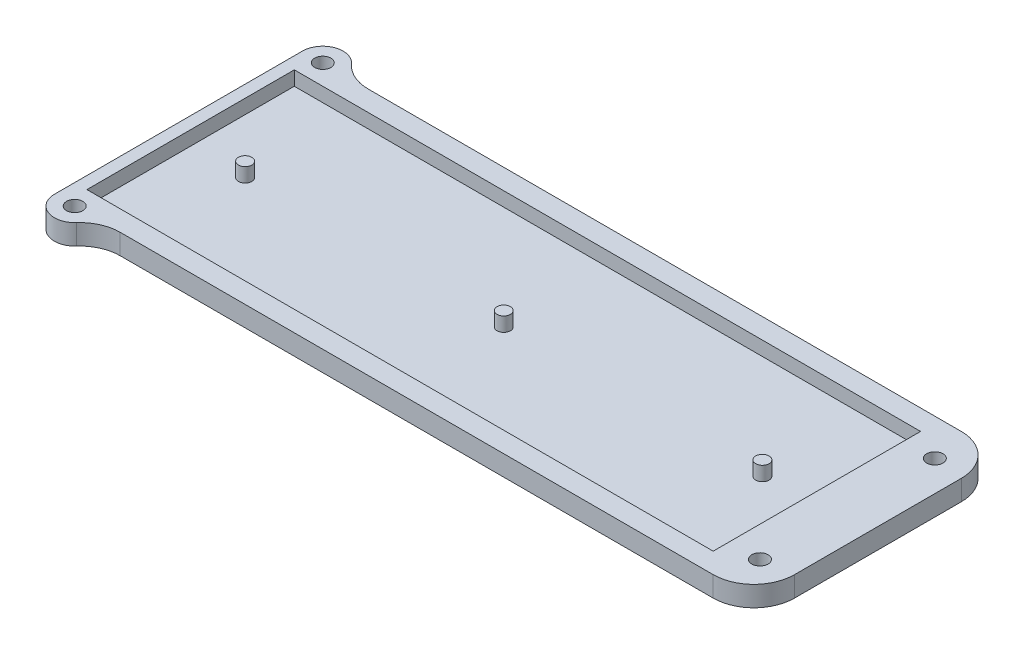
SolidWorks part; units mm, degrees
ref_plane "Front Plane" through (0, 0, 0) normal (0, 0, 1) x (1, 0, 0)
ref_plane "Top Plane" through (0, 0, 0) normal (0, 1, 0) x (1, 0, 0)
ref_plane "Right Plane" through (0, 0, 0) normal (1, 0, 0) x (0, 0, -1)
sketch "Sketch2" plane through (0, 0, 0) normal (0, 1, 0) x (1, 0, 0)
  line L1 (172, 0) -> (172, 61)
  line L3 (0, 61) -> (0, 0)
  line L4 (0, 30.5) -> (172, 30.5) construction
  line L5 (3, 56) -> (157, 56) construction
  line L6 (3, 56) -> (3, 5) construction
  line L7 (3, 5) -> (157, 5) construction
  line L8 (157, 56) -> (157, 5) construction
  line L9 (3, 56) -> (157, 5) construction
  line L10 (3, 5) -> (157, 56) construction
  line L12 (10, 0) -> (172, 0)
  line L13 (10, 61) -> (172, 61)
  line L14 (10, 0) -> (0, 0) construction
  line L15 (10, 61) -> (0, 61) construction
  circle A1 centre (164.5, 9) radius 2
  circle A2 centre (164.5, 52) radius 2
  circle A3 centre (5, 0) radius 2
  circle A4 centre (5, 61) radius 2
  arc A5 (0, 61) -> (10, 61) centre (5, 61) cw
  arc A6 (0, 0) -> (10, 0) centre (5, 0) ccw
  point P3 (80, 30.5)
  point P23 (8.4054, 59.8523)
  point P24 (9.6845, 61)
  point P25 (8.8708, 0)
  point P26 (10, 0)
  point P27 (0, 0)
  dimension "D5" = 15
  dimension "D4" = 4
  dimension "D7" = 3
  dimension "D9" = 4
  dimension "D1" = 51
  dimension "D2" = 154
  dimension "D3" = 5
  dimension "D6" = 7.5
  dimension "D8" = 61
  dimension "D10" = 5
  dimension "D11" = 9
extrude "Boss-Extrude1" add sketch "Sketch2" along normal blind 5
sketch "Sketch3" plane through (0, 5, 0) normal (0, 1, 0) x (1, 0, 0)
  line L0 (0, 30.5) -> (172, 30.5) construction
  line L1 (3, 56) -> (157, 56)
  line L2 (3, 56) -> (3, 5)
  line L3 (3, 5) -> (157, 5)
  line L4 (157, 56) -> (157, 5)
  line L5 (3, 56) -> (157, 5) construction
  line L6 (3, 5) -> (157, 56) construction
  line L7 (0, 61) -> (0, 0) construction
  line L8 (172, 0) -> (172, 61) construction
  line L9 (172, 61) -> (10, 61) construction
  line L10 (172, 0) -> (172, 61) construction
  circle A0 centre (80, 30.5) radius 1.65
  circle A1 centre (16.4, 30.5) radius 1.65
  circle A2 centre (143.6, 30.5) radius 1.65
  point P0 (80, 30.5)
  point P13 (0, 0)
  dimension "D5" = 3.3
  dimension "D1" = 51
  dimension "D2" = 154
  dimension "D3" = 13.4
  dimension "D4" = 13.4
  dimension "D6" = 15
  dimension "D7" = 5
extrude "Cut-Extrude1" cut sketch "Sketch3" against normal blind 3.5
fillet "Fillet1" radius 10 4 edges at (172, 2.5, 0) (172, 2.5, -61) (10, 2.5, -61) (10, 2.5, 0)
